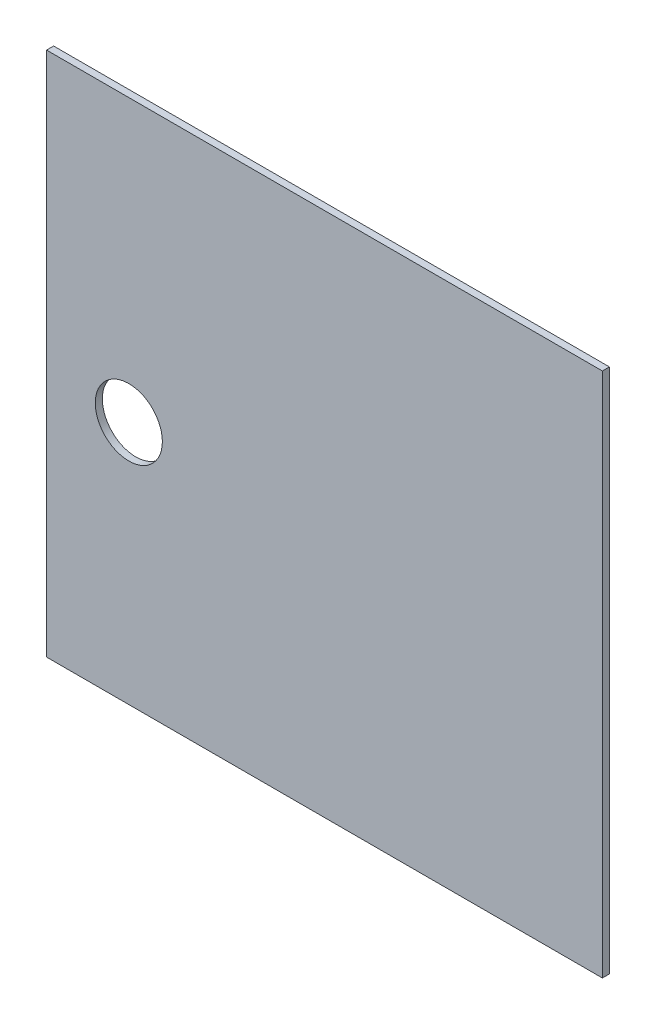
SolidWorks part; units mm, degrees
ref_plane "Front Plane" through (0, 0, 0) normal (0, 0, 1) x (1, 0, 0)
ref_plane "Top Plane" through (0, 0, 0) normal (0, 1, 0) x (1, 0, 0)
ref_plane "Right Plane" through (0, 0, 0) normal (1, 0, 0) x (0, 0, -1)
sketch "Sketch1" plane through (0, 0, 0) normal (0, 0, 1) x (1, 0, 0)
  line L1 (0, 0) -> (236.55, 0)
  line L2 (0, 0) -> (0, 223.74)
  line L3 (0, 223.74) -> (236.55, 223.74)
  line L4 (236.55, 0) -> (236.55, 223.74)
  dimension "D1" = 236.55
  dimension "D2" = 223.74
extrude "Boss-Extrude1" add sketch "Sketch1" along normal blind 3
sketch "Sketch2" plane through (0, 0, 3) normal (0, 0, 1) x (1, 0, 0)
  line L0 (236.55, 223.74) -> (0, 223.74) construction
  line L2 (0, 223.74) -> (0, 0) construction
  circle A0 centre (35, 104.05) radius 14.275
  dimension "D1" = 28.55
  dimension "D2" = 35
  dimension "D3" = 119.69
extrude "Cut-Extrude1" cut sketch "Sketch2" against normal blind 3
